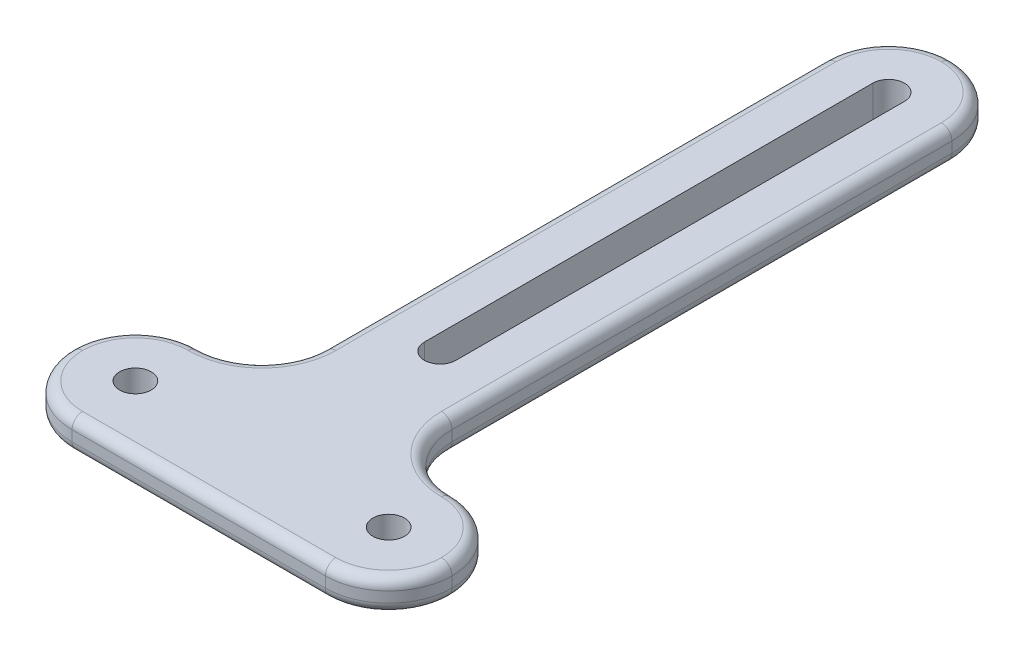
SolidWorks part; units mm, degrees
material "6061 Alloy"
ref_plane "Front Plane" through (0, 0, 0) normal (0, 0, 1) x (1, 0, 0)
ref_plane "Top Plane" through (0, 0, 0) normal (0, 1, 0) x (1, 0, 0)
ref_plane "Right Plane" through (0, 0, 0) normal (1, 0, 0) x (0, 0, -1)
sketch "Sketch1" plane through (0, 0, 0) normal (0, 1, 0) x (1, 0, 0)
  line L0 (0, 0) -> (133.35, 0) construction
  line L5 (133.35, 0) -> (133.35, 35.731) construction
  line L6 (133.35, 35.731) -> (0, 0) construction
  line L7 (133.35, 125.6694) -> (76.2, 0) construction
  line L8 (133.35, 125.6694) -> (133.35, 35.731) construction
  line L9 (133.35, 0) -> (158.75, 0) construction
  line L10 (120.65, 12.7) -> (120.65, 138.3694)
  line L11 (95.25, -12.7) -> (120.65, -12.7)
  line L12 (95.25, -12.7) -> (95.25, 12.7)
  line L13 (95.25, 12.7) -> (120.65, 12.7)
  line L14 (120.65, -12.7) -> (120.65, 12.7) construction
  line L15 (95.25, -12.7) -> (120.65, 12.7) construction
  line L16 (95.25, 12.7) -> (120.65, -12.7) construction
  line L17 (120.65, 138.3694) -> (146.05, 138.3694)
  line L18 (146.05, 138.3694) -> (146.05, 12.7)
  line L19 (120.65, -12.7) -> (146.05, -12.7)
  line L20 (171.45, -12.7) -> (146.05, -12.7)
  line L21 (171.45, -12.7) -> (171.45, 12.7)
  line L22 (171.45, 12.7) -> (146.05, 12.7)
  line L23 (146.05, -12.7) -> (146.05, 12.7) construction
  line L24 (171.45, -12.7) -> (146.05, 12.7) construction
  line L25 (171.45, 12.7) -> (146.05, -12.7) construction
  line L26 (130.175, 125.6694) -> (130.175, 35.731)
  line L27 (136.525, 35.731) -> (136.525, 125.6694)
  circle A3 centre (133.35, 125.6694) radius 3.175
  circle A4 centre (107.95, 0) radius 3.175
  circle A5 centre (158.75, 0) radius 3.175
  circle A6 centre (133.35, 35.731) radius 3.175
  point P7 (130.175, 35.731)
  point P27 (0, 0)
  point P28 (136.525, 35.731)
  point P29 (130.0451, 125.6694)
  point P30 (136.6549, 125.6694)
  point P31 (130.0451, 125.6694)
  point P32 (133.35, 35.731)
  dimension "D3" = 76.2
  dimension "D1" = 15
  dimension "D8" = 25.4
  dimension "D4" = 6.35
  dimension "D2" = 133.35
  dimension "D5" = 25.4
  dimension "D6" = 25.4
  dimension "D7" = 25.4
  dimension "D9" = 12.7
extrude "Boss-Extrude1" add sketch "Sketch1" along normal blind 6.35 contours L21 L22 L18 L17 L10 L13 L12 L11 L19 L20 A6 L26 A3 L27 A5 A4 region at (122.342, 0, -75.5347)
fillet "Fillet2" radius 12.7 8 edges at (120.65, 3.175, -138.3694) (146.05, 3.175, -138.3694) (146.05, 3.175, -12.7) (171.45, 3.175, 12.7) (171.45, 3.175, -12.7) (95.25, 3.175, 12.7) (95.25, 3.175, -12.7) (120.65, 3.175, -12.7)
fillet "Fillet3" radius 2.1167 22 edges at (142.3303, 0, -134.6497) (124.3697, 0, -134.6497) (120.65, 0, -75.5347) (116.9303, 0, -16.4197) (98.9697, 0, -8.9803) (98.9697, 0, 8.9803) (133.35, 0, 12.7) (167.7303, 0, 8.9803) (167.7303, 0, -8.9803) (149.7697, 0, -16.4197) (142.3303, 6.35, -134.6497) (124.3697, 6.35, -134.6497) (120.65, 6.35, -75.5347) (116.9303, 6.35, -16.4197) (98.9697, 6.35, -8.9803) (98.9697, 6.35, 8.9803) (133.35, 6.35, 12.7) (167.7303, 6.35, 8.9803) (167.7303, 6.35, -8.9803) (149.7697, 6.35, -16.4197) (146.05, 0, -75.5347) (146.05, 6.35, -75.5347)
